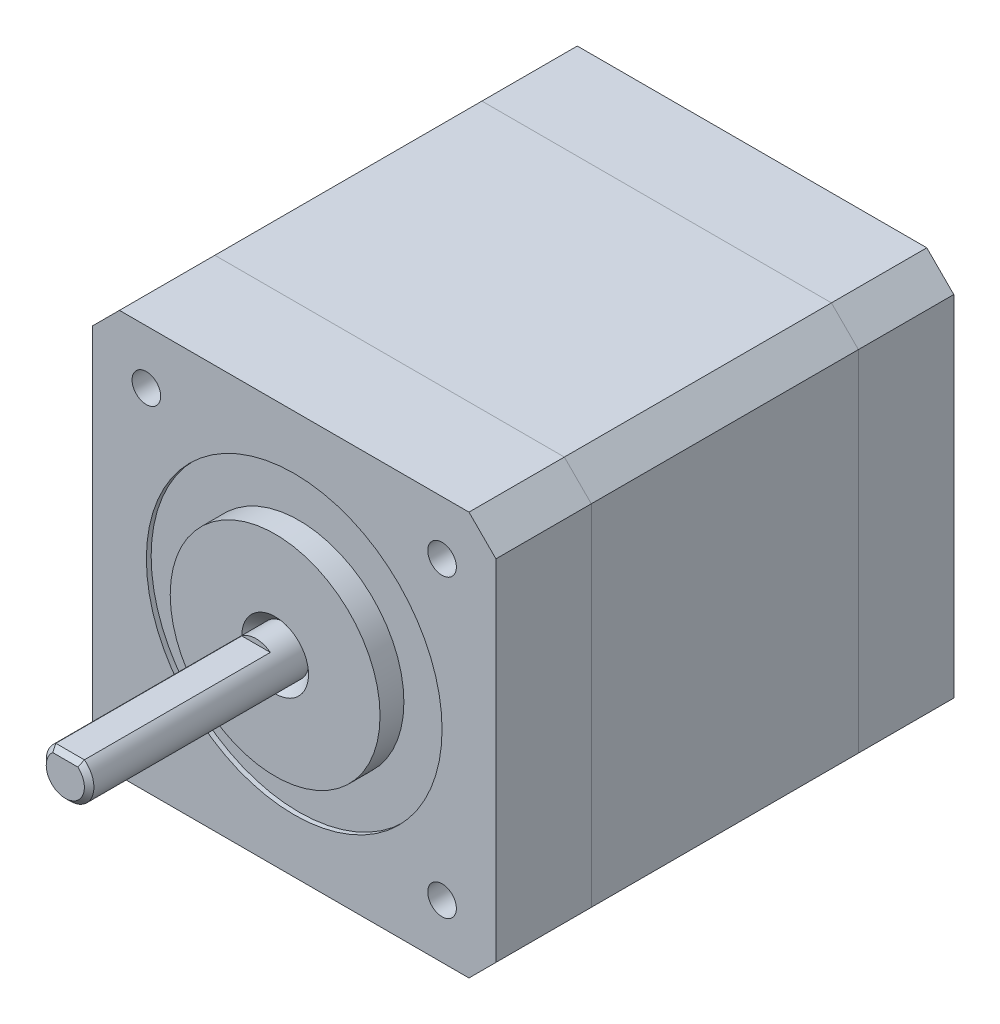
SolidWorks part; units mm, degrees
material "自定义塑料"
ref_plane "前视基准面" through (0, 0, 0) normal (0, 0, 1) x (1, 0, 0)
ref_plane "上视基准面" through (0, 0, 0) normal (0, 1, 0) x (1, 0, 0)
ref_plane "右视基准面" through (0, 0, 0) normal (1, 0, 0) x (0, 0, -1)
sketch "草图1" plane through (0, 0, 0) normal (0, 0, 1) x (1, 0, 0)
  line L0 (0, -21.15) -> (0, 21.15) construction
  line L1 (18.3216, 21.15) -> (-18.3216, 21.15)
  line L2 (-18.3216, 21.15) -> (-21.15, 18.3216)
  line L3 (-21.15, 18.3216) -> (-21.15, -18.3216)
  line L4 (-21.15, -18.3216) -> (-18.3216, -21.15)
  line L5 (-18.3216, -21.15) -> (18.3216, -21.15)
  line L6 (21.15, -18.3216) -> (18.3216, -21.15)
  line L7 (18.3216, 21.15) -> (21.15, 18.3216)
  line L8 (21.15, 18.3216) -> (21.15, -18.3216)
  line L9 (-19.7358, 19.7358) -> (0, 0) construction
  line L10 (-15.5, 15.5) -> (15.5, 15.5) construction
  circle A0 centre (-15.5, 15.5) radius 1.5
  circle A1 centre (15.5, 15.5) radius 1.5
  circle A2 centre (15.5, -15.5) radius 1.5
  circle A3 centre (-15.5, -15.5) radius 1.5
  circle A4 centre (0, 0) radius 15.5
  circle A6 centre (0, 0) radius 11
  circle A8 centre (0, 0) radius 2.5
  dimension "D5" = 3
  dimension "D8" = 5
  dimension "D9" = 22
  dimension "D1" = 135
  dimension "D2" = 42.3
  dimension "D3" = 42.3
  dimension "D4" = 4
  dimension "D6" = 31
  dimension "D7" = 4
extrude "凸台-拉伸1" add sketch "草图1" against normal blind 10 contours L8 L7 L1 L2 L3 L4 L5 L6 A4 A3 A2 A1 A0 | A4 | A6 | A6 | A8 | A8 region at (19.3128, 19.3128, 0) region at (-15.0616, 0, 0) region at (-10.6889, 0, 0) region at (0, 0, 0)
sketch "草图2" plane through (0, 0, -10) normal (0, 0, -1) x (-1, 0, 0)
  line L8 (-21.15, 18.3216) -> (-21.15, -18.3216)
  line L9 (-21.15, -18.3216) -> (-18.3216, -21.15)
  line L10 (-18.3216, -21.15) -> (18.3216, -21.15)
  line L11 (18.3216, -21.15) -> (21.15, -18.3216)
  line L12 (21.15, -18.3216) -> (21.15, 18.3216)
  line L13 (21.15, 18.3216) -> (18.3216, 21.15)
  line L14 (18.3216, 21.15) -> (-18.3216, 21.15)
  line L15 (-18.3216, 21.15) -> (-21.15, 18.3216)
  line L16 (-21.15, 18.3216) -> (-21.15, -18.3216)
  line L17 (-21.15, -18.3216) -> (-18.3216, -21.15)
  line L18 (-18.3216, -21.15) -> (18.3216, -21.15)
  line L19 (18.3216, -21.15) -> (21.15, -18.3216)
  line L20 (21.15, -18.3216) -> (21.15, 18.3216)
  line L21 (21.15, 18.3216) -> (18.3216, 21.15)
  line L22 (18.3216, 21.15) -> (-18.3216, 21.15)
  line L23 (-18.3216, 21.15) -> (-21.15, 18.3216)
  dimension "D1" = 0
extrude "凸台-拉伸2" add sketch "草图2" along normal blind 28 separate body
sketch "草图3" plane through (0, 0, -38) normal (0, 0, -1) x (-1, 0, 0)
  line L8 (-18.3216, 21.15) -> (-21.15, 18.3216)
  line L9 (-21.15, 18.3216) -> (-21.15, -18.3216)
  line L10 (-21.15, -18.3216) -> (-18.3216, -21.15)
  line L11 (-18.3216, -21.15) -> (18.3216, -21.15)
  line L12 (18.3216, -21.15) -> (21.15, -18.3216)
  line L13 (21.15, -18.3216) -> (21.15, 18.3216)
  line L14 (21.15, 18.3216) -> (18.3216, 21.15)
  line L15 (18.3216, 21.15) -> (-18.3216, 21.15)
  line L16 (-18.3216, 21.15) -> (-21.15, 18.3216)
  line L17 (-21.15, 18.3216) -> (-21.15, -18.3216)
  line L18 (-21.15, -18.3216) -> (-18.3216, -21.15)
  line L19 (-18.3216, -21.15) -> (18.3216, -21.15)
  line L20 (18.3216, -21.15) -> (21.15, -18.3216)
  line L21 (21.15, -18.3216) -> (21.15, 18.3216)
  line L22 (21.15, 18.3216) -> (18.3216, 21.15)
  line L23 (18.3216, 21.15) -> (-18.3216, 21.15)
  dimension "D1" = 0
extrude "凸台-拉伸3" add sketch "草图3" along normal blind 10 separate body
extrude "切除-拉伸1" cut sketch "草图1<3>" against normal blind 0.5 contours A4 region at (-15.0616, 0, 0)
sketch "草图1<3>" plane through (0, 0, 0) normal (0, 0, 1) x (1, 0, 0) same geometry as "草图1"
extrude "凸台-拉伸4" add sketch "草图1<4>" along normal blind 2 contours A6 region at (-10.6889, 0, 0)
sketch "草图1<4>" plane through (0, 0, 0) normal (0, 0, 1) x (1, 0, 0) same geometry as "草图1"
chamfer "倒角1" distance 1 1 edges at (2.5, 0, 2)
extrude "凸台-拉伸5" add sketch "草图1<5>" along normal blind 24 separate body contours A8 region at (0, 0, 0)
sketch "草图1<5>" plane through (0, 0, 0) normal (0, 0, 1) x (1, 0, 0) same geometry as "草图1"
sketch "草图4" plane through (0, 0, 24) normal (0, 0, 1) x (1, 0, 0)
  line L0 (-1.5, 2) -> (1.5, 2)
  circle A1 centre (0, 0) radius 2.5
  arc A2 (1.5, 2) -> (-1.5, 2) centre (0, 0) ccw
  dimension "D2" = 0.5
  dimension "D1" = 0
extrude "切除-拉伸2" cut sketch "草图4" against normal blind 20
chamfer "倒角2" distance 0.5 2 edges at (0, 2, 24) (0, -2.5, 24)
